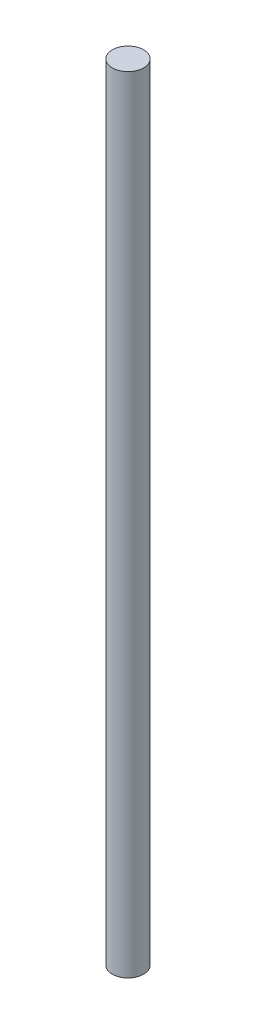
SolidWorks part; units mm, degrees
ref_plane "Front Plane" through (0, 0, 0) normal (0, 0, 1) x (1, 0, 0)
ref_plane "Top Plane" through (0, 0, 0) normal (0, 1, 0) x (1, 0, 0)
ref_plane "Right Plane" through (0, 0, 0) normal (1, 0, 0) x (0, 0, -1)
sketch "Sketch2" plane through (0, 0, 0) normal (0, 1, 0) x (1, 0, 0)
  circle A0 centre (0, 0) radius 2
  dimension "D1" = 4
extrude "Boss-Extrude1" add sketch "Sketch2" along normal blind 100
